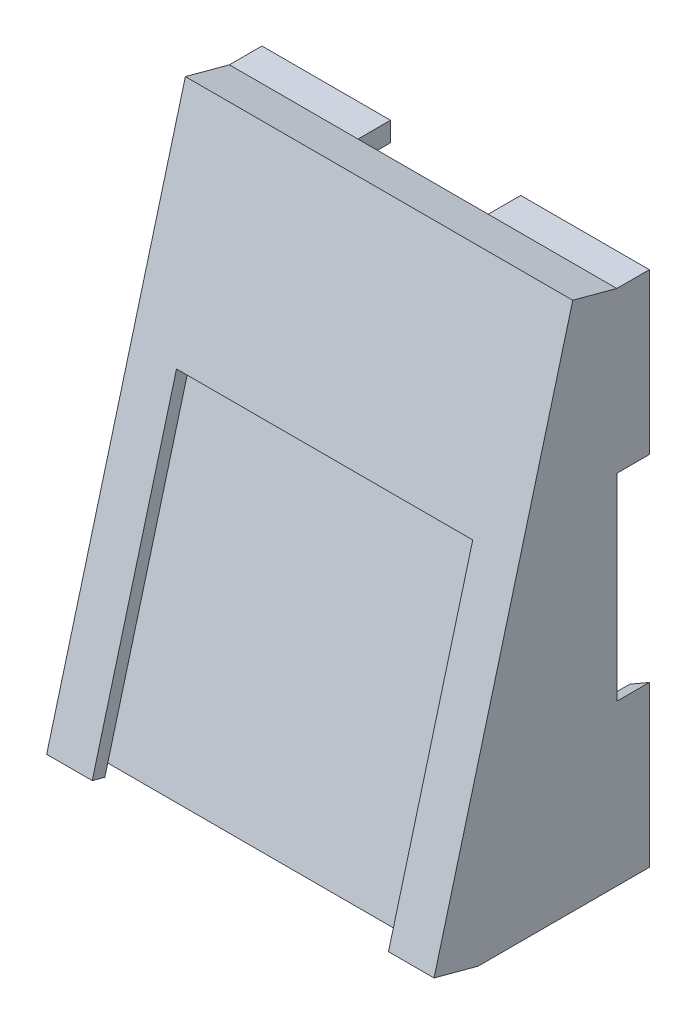
SolidWorks part; units mm, degrees
ref_plane "Front Plane" through (0, 0, 0) normal (1, 0, 0) x (0, 1, 0)
ref_plane "Top Plane" through (0, 0, 0) normal (0, 0, 1) x (0, 1, 0)
ref_plane "Right Plane" through (0, 0, 0) normal (0, 1, 0) x (-1, 0, 0)
sketch "Sketch3" plane through (0, 0, 0) normal (1, 0, 0) x (0, 1, 0)
  line L0 (-39.75, 2.5) -> (-39.75, 23.802)
  line L1 (-39.75, -2.5) -> (39.75, -2.5)
  line L2 (-39.75, -2.5) -> (-39.75, 2.5)
  line L3 (-39.75, 2.5) -> (39.75, 2.5)
  line L4 (39.75, -2.5) -> (39.75, 2.5)
  line L5 (-39.75, -2.5) -> (39.75, 2.5) construction
  line L6 (-39.75, 2.5) -> (39.75, -2.5) construction
  line L7 (-37.9383, 30.5634) -> (41.5617, 9.2615)
  line L8 (41.5617, 9.2615) -> (39.75, 2.5)
  line L9 (39.75, 2.5) -> (-39.75, 23.802)
  line L10 (-39.75, 23.802) -> (-37.9383, 30.5634)
  point P0 (0, 0)
  dimension "D1" = 15
  dimension "D2" = 90
  dimension "D3" = 7
  dimension "D4" = 79.5
  dimension "D5" = 5
  dimension "D6" = 82.3045
extrude "Boss-Extrude1" add sketch "Sketch3" along normal blind 59.5 contours L1 L4 L3 L2 | L3 L9 L0 | L10 L9 L8 L7 region at (0, 0, 0) region at (0, -13.25, 9.6007) region at (0, 0.9059, 16.5317)
sketch "Sketch4" plane through (0, -43.0377, 11.5319) normal (0, -0.9659, 0.2588) x (1, 0, 0)
  line L1 (2, 17.7029) -> (57.5, 17.7029)
  line L2 (2, 17.7029) -> (2, 14.7029)
  line L3 (2, 14.7029) -> (57.5, 14.7029)
  line L4 (57.5, 17.7029) -> (57.5, 14.7029)
  line L5 (0, -55) -> (0, 55) construction
  line L6 (59.5, 12.7029) -> (59.5, 19.7029) construction
  line L7 (59.5, 19.7029) -> (0, 19.7029) construction
  line L8 (59.5, 12.7029) -> (0, 12.7029) construction
  dimension "D1" = 2
  dimension "D2" = 2
  dimension "D3" = 55.5
  dimension "D4" = 2
  dimension "D5" = 2
  dimension "D6" = 3
extrude "Cut-Extrude1" cut sketch "Sketch4" against normal blind 80
sketch "Sketch5" plane through (0, -43.0377, 11.5319) normal (0, -0.9659, 0.2588) x (1, 0, 0)
  line L0 (59.5, 19.7029) -> (0, 19.7029) construction
  line L1 (7, 19.7029) -> (52.5, 19.7029)
  line L2 (7, 19.7029) -> (7, 17.7029)
  line L3 (7, 17.7029) -> (52.5, 17.7029)
  line L4 (52.5, 19.7029) -> (52.5, 17.7029)
  line L6 (2, 17.7029) -> (2, 14.7029) construction
  line L7 (57.5, 17.7029) -> (2, 17.7029) construction
  line L8 (57.5, 14.7029) -> (57.5, 17.7029) construction
  dimension "D1" = 5
  dimension "D2" = 5
extrude "Cut-Extrude2" cut sketch "Sketch5" against normal blind 50
sketch "Sketch6" plane through (59.5, 0, 0) normal (1, 0, 0) x (0, 1, 0)
  line L0 (-36.75, -6.8985) -> (-36.75, 22.5111)
  line L1 (-36.75, 22.5111) -> (36.75, 2.8169)
  line L2 (36.75, 2.8169) -> (36.75, -6.8985)
  line L3 (36.75, -6.8985) -> (-36.75, -6.8985)
  line L5 (-39.75, -2.5) -> (-39.75, 23.802) construction
  line L6 (39.75, -2.5) -> (39.75, 2.5) construction
  line L7 (-37.9383, 30.5634) -> (41.5617, 9.2615) construction
  dimension "D1" = 15
  dimension "D2" = 3
  dimension "D3" = 3
  dimension "D4" = 7.4704
extrude "Cut-Extrude3" cut sketch "Sketch6" against normal blind 53.5 from offset 3 offset against normal yes
sketch "Sketch7" plane through (0, 0, -2.5) normal (0, 0, -1) x (1, 0, 0)
  line L2 (38.6799, 36.75) -> (20.3201, 36.75)
  line L3 (3, 36.75) -> (56.5, 36.75) construction
  line L4 (3, -36.75) -> (3, 36.75) construction
  line L6 (3, -16.8875) -> (-26.25, 0)
  line L7 (-26.25, 0) -> (3, 16.8875)
  line L8 (3, -16.8875) -> (3, 16.8875)
  line L11 (3, -39.7076) -> (3, -5.9326)
  line L14 (3, -62.5278) -> (3, -28.7528)
  line L15 (59.5, 39.75) -> (0, 39.75) construction
  line L17 (29.75, 39.75) -> (29.75, -39.75) construction
  line L18 (59.5, -39.75) -> (0, -39.75) construction
  line L19 (56.5, -62.5278) -> (56.5, -28.7528)
  line L20 (56.5, -39.7076) -> (56.5, -5.9326)
  line L21 (56.5, -16.8875) -> (56.5, 16.8875)
  line L28 (-18.1849, 0) -> (18.1849, 0) construction
  line L29 (38.6799, -36.75) -> (20.3201, -36.75)
  line L32 (3, -39.7076) -> (-26.25, -22.8201) [skipped]
  line L33 (-26.25, -22.8201) -> (3, -5.9326) [skipped]
  line L34 (3, -62.5278) -> (-26.25, -45.6403) [skipped]
  line L35 (-26.25, -45.6403) -> (3, -28.7528) [skipped]
  line L36 (85.75, 0) -> (56.5, 16.8875)
  line L37 (19.75, 34.3332) -> (39.75, 34.3332)
  line L38 (19.75, 34.3332) -> (19.75, 45.1668)
  line L39 (19.75, 45.1668) -> (39.75, 45.1668)
  line L40 (39.75, 34.3332) -> (39.75, 45.1668)
  line L41 (19.75, 34.3332) -> (39.75, 45.1668) construction
  line L42 (19.75, 45.1668) -> (39.75, 34.3332) construction
  line L43 (19.75, -44.4839) -> (39.75, -44.4839)
  line L44 (19.75, -44.4839) -> (19.75, -30.9705)
  line L45 (19.75, -30.9705) -> (39.75, -30.9705)
  line L46 (39.75, -44.4839) -> (39.75, -30.9705)
  line L47 (19.75, -44.4839) -> (39.75, -30.9705) construction
  line L48 (19.75, -30.9705) -> (39.75, -44.4839) construction
  line L49 (56.5, -16.8875) -> (85.75, 0)
  circle A1 centre (-6.75, 0) radius 9.75
  circle A8 centre (-6.75, -22.8201) radius 9.75 [skipped]
  circle A9 centre (-6.75, -45.6403) radius 9.75 [skipped]
  circle A10 centre (66.25, 0) radius 9.75
  point P10 (29.75, -37.7272)
  line M5 (56.5, -36.75) -> (3, -36.75)
  line M7 (3, 36.75) -> (56.5, 36.75)
  line M10 (0, -39.75) -> (59.5, -39.75)
  line M12 (59.5, 39.75) -> (0, 39.75)
  dimension "D1" = 20
  dimension "D4" = 19.5
  dimension "D2" = 0
  dimension "D3" = 20
  dimension "D5" = 0
  dimension "D7" = 39.75
  dimension "D6" = 3
extrude "Cut-Extrude4" cut sketch "Sketch7" against normal blind 5 contours L40 L38 M7 M12 | L46 L44 M10 M5 | L6 L7 L8 | L21 L36 L49 region at (29.75, -38.25, -2.5) region at (29.75, 38.25, -2.5)
